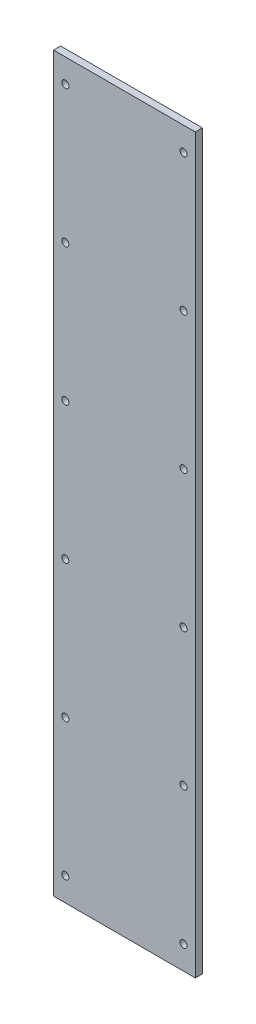
SolidWorks part; units mm, degrees
ref_plane "Plan de face" through (0, 0, 0) normal (0, 0, 1) x (1, 0, 0)
ref_plane "Plan de dessus" through (0, 0, 0) normal (0, 1, 0) x (1, 0, 0)
ref_plane "Plan de droite" through (0, 0, 0) normal (1, 0, 0) x (0, 0, -1)
sketch "Esquisse1" plane through (0, 0, 0) normal (0, 0, 1) x (1, 0, 0)
  line L0 (-30, 0) -> (30, 0) construction
  line L1 (30, -155) -> (-30, -155)
  line L2 (30, -155) -> (30, 155)
  line L3 (30, 155) -> (-30, 155)
  line L4 (-30, -155) -> (-30, 155)
  line L5 (30, -155) -> (-30, 155) construction
  line L6 (30, 155) -> (-30, -155) construction
  line L7 (-30, -155) -> (-20, -155)
  line L8 (-30, -155) -> (-30, -150)
  line L13 (-30, 155) -> (-20, 155)
  line L14 (-30, 155) -> (-30, 150)
  line L15 (-25, -155) -> (-25, 155) construction
  line L16 (0, 155) -> (0, -155) construction
  line L17 (-25, -145) -> (-25, -87) construction
  circle A0 centre (-25, -145) radius 1.5
  circle A1 centre (-25, -87) radius 1.5
  circle A2 centre (-25, -29) radius 1.5
  circle A3 centre (-25, 29) radius 1.5
  circle A4 centre (-25, 87) radius 1.5
  circle A5 centre (-25, 145) radius 1.5
  circle A6 centre (25, -87) radius 1.5
  circle A7 centre (25, -145) radius 1.5
  circle A8 centre (25, -29) radius 1.5
  circle A9 centre (25, 29) radius 1.5
  circle A10 centre (25, 87) radius 1.5
  circle A11 centre (25, 145) radius 1.5
  point P0 (0, 0)
  dimension "D5" = 3
  dimension "D1" = 60
  dimension "D2" = 310
  dimension "D7" = 58
  dimension "D8" = 6
extrude "Boss.-Extru.1" add sketch "Esquisse1" along normal blind 3 contours L3 L4 L1 L2 A10 A8 A6 A5 A4 A3 A2 A1 A0 A7 A9 A11 region at (0, 0, 0)
